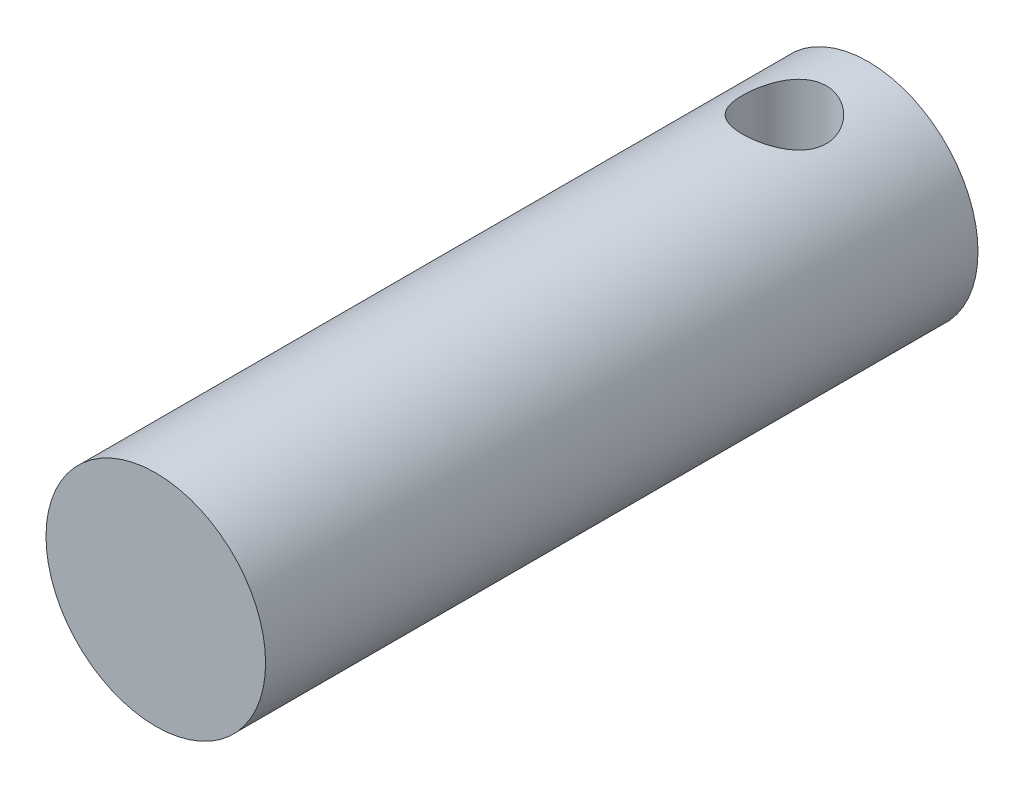
SolidWorks part; units mm, degrees
ref_plane "Front Plane" through (0, 0, 0) normal (0, 0, 1) x (1, 0, 0)
ref_plane "Top Plane" through (0, 0, 0) normal (0, 1, 0) x (1, 0, 0)
ref_plane "Right Plane" through (0, 0, 0) normal (1, 0, 0) x (0, 0, -1)
sketch "Sketch1" plane through (0, 0, 0) normal (0, 0, 1) x (1, 0, 0)
  circle A0 centre (0, 0) radius 2.62
  dimension "D1" = 5.24
extrude "Boss-Extrude1" add sketch "Sketch1" along normal blind 17
sketch "Sketch2" plane through (0, 0, 0) normal (0, 1, 0) x (1, 0, 0)
  line L0 (2.62, 0) -> (-2.62, 0) construction
  line L1 (2.62, 0) -> (-2.62, 0)
  circle A0 centre (0, -2) radius 1
extrude "Cut-Extrude1" cut sketch "Sketch2" against normal blind 10 and the other way blind 10 contours A0 region at (0, 0, 2)
